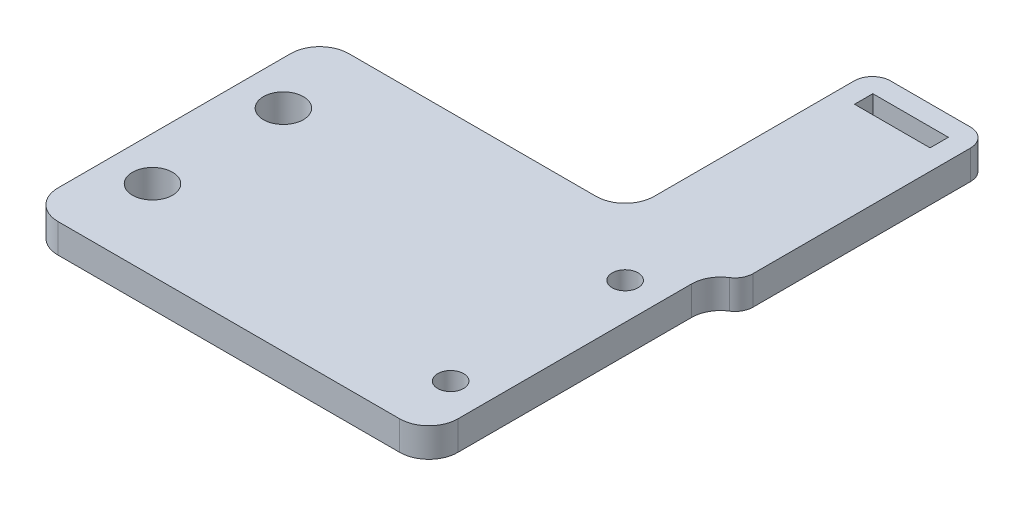
SolidWorks part; units mm, degrees
ref_plane "Front" through (0, 0, 0) normal (0, 0, 1) x (1, 0, 0)
ref_plane "Top" through (0, 0, 0) normal (0, 1, 0) x (1, 0, 0)
ref_plane "Right" through (0, 0, 0) normal (1, 0, 0) x (0, 0, -1)
sketch "Sketch1" plane through (0, 0, 0) normal (0, 1, 0) x (1, 0, 0)
  line L1 (0, 0) -> (34.925, 0)
  line L2 (0, 0) -> (0, 25.4)
  line L3 (0, 25.4) -> (34.925, 25.4)
  line L4 (34.925, 0) -> (34.925, 25.4)
  dimension "D1" = 25.4
  dimension "D2" = 34.925
extrude "Boss-Extrude1" add sketch "Sketch1" along normal blind 2.54
sketch "Sketch2" plane through (0, 2.54, 0) normal (0, 1, 0) x (1, 0, 0)
  line L0 (0, 12.7) -> (34.925, 12.7) construction
  line L1 (0, 25.4) -> (0, 0) construction
  line L2 (34.925, 0) -> (34.925, 25.4) construction
  circle A0 centre (3.81, 18.415) radius 1.7462
  circle A1 centre (3.81, 6.985) radius 1.7463
  dimension "D1" = 3.4925
  dimension "D2" = 5.715
  dimension "D3" = 3.81
extrude "Cut-Extrude3" cut sketch "Sketch2" along normal through all and the other way through all
sketch "Sketch5" plane through (0, 2.54, 0) normal (0, 1, 0) x (1, 0, 0)
  line L0 (0, 12.7) -> (34.925, 12.7) construction
  line L1 (0, 25.4) -> (0, 0) construction
  line L2 (34.925, 0) -> (34.925, 25.4) construction
  line L3 (34.925, 25.4) -> (0, 25.4) construction
  circle A0 centre (31.75, 20.32) radius 1.1303
  circle A1 centre (31.75, 5.08) radius 1.1303
  dimension "D1" = 2.2606
  dimension "D2" = 5.08
  dimension "D3" = 3.175
extrude "Cut-Extrude4" cut sketch "Sketch5" against normal through all
sketch "Sketch6" plane through (0, 2.54, 0) normal (0, 1, 0) x (1, 0, 0)
  line L0 (31.75, 20.32) -> (31.75, 5.08) construction
  line L1 (31.75, 20.32) -> (31.75, 38.7587) construction
  line L2 (34.925, 25.4) -> (0, 25.4) construction
  line L3 (36.83, 46.99) -> (26.67, 46.99)
  line L4 (36.83, 46.99) -> (36.83, 25.4)
  line L5 (36.83, 25.4) -> (26.67, 25.4)
  line L6 (26.67, 46.99) -> (26.67, 25.4)
  line L7 (36.83, 46.99) -> (26.67, 25.4) construction
  line L8 (36.83, 25.4) -> (26.67, 46.99) construction
  point P5 (31.75, 36.195)
  point P12 (31.75, 12.7)
  dimension "D1" = 34.29
  dimension "D2" = 10.16
extrude "Boss-Extrude2" add sketch "Sketch6" against normal blind 2.54
fillet "Fillet1" radius 2.54 2 edges at (34.925, 1.27, -25.4) (26.67, 1.27, -25.4)
fillet "Fillet2" radius 1.5875 3 edges at (36.83, 1.27, -46.99) (26.67, 1.27, -46.99) (36.83, 1.27, -25.4)
fillet "Fillet3" radius 2.54 3 edges at (0, 1.27, 0) (0, 1.27, -25.4) (34.925, 1.27, 0)
sketch "Sketch8" plane through (0, 2.54, 0) normal (0, 1, 0) x (1, 0, 0)
  line L0 (31.75, 5.08) -> (31.75, 20.3549) construction
  line L1 (31.75, 20.3549) -> (31.75, 46.99) construction
  line L2 (35.2425, 46.99) -> (28.2575, 46.99) construction
  line L4 (28.4514, 45.2501) -> (35.0486, 45.2501)
  line L5 (28.4514, 45.2501) -> (28.4514, 43.6499)
  line L6 (28.4514, 43.6499) -> (35.0486, 43.6499)
  line L7 (35.0486, 45.2501) -> (35.0486, 43.6499)
  line L8 (28.4514, 45.2501) -> (35.0486, 43.6499) construction
  line L9 (28.4514, 43.6499) -> (35.0486, 45.2501) construction
  point P3 (31.75, 44.45)
  dimension "D1" = 1.6002
  dimension "D2" = 6.5973
  dimension "D3" = 2.54
extrude "Cut-Extrude6" cut sketch "Sketch8" against normal blind 2.54
